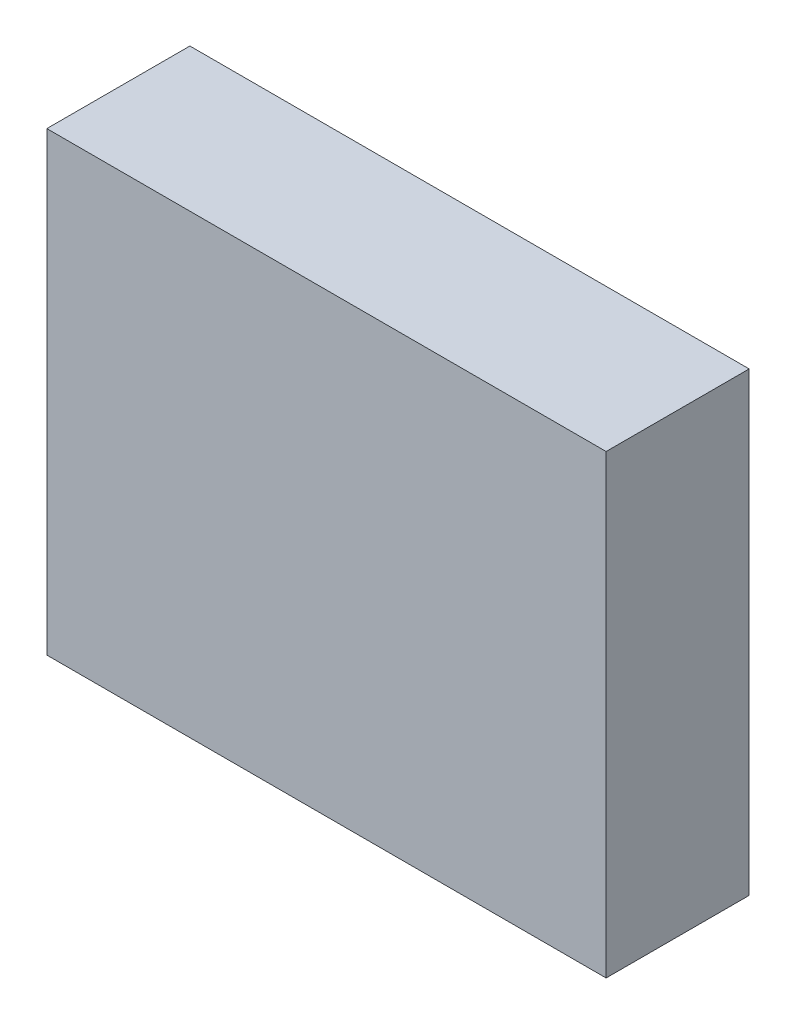
SolidWorks part; units mm, degrees
material "AISI 1020"
ref_plane "Plano superior" through (0, 0, 0) normal (0, 0, 1) x (1, 0, 0)
ref_plane "Plano frontal" through (0, 0, 0) normal (0, 1, 0) x (1, 0, 0)
ref_plane "Plano direito" through (0, 0, 0) normal (1, 0, 0) x (0, 0, -1)
other "Caixa delimitadora"
ref_plane "Default Plane" through (-78.1989, -63.755, 0) normal (0, 1, 0) x (1, 0, 0)
sketch "Esboço1" plane through (0, 0, 0) normal (0, 0, 1) x (1, 0, 0)
  line L1 (-78.1989, -63.755) -> (78.1989, -63.755)
  line L2 (-78.1989, -63.755) -> (-78.1989, 63.755)
  line L3 (-78.1989, 63.755) -> (78.1989, 63.755)
  line L4 (78.1989, -63.755) -> (78.1989, 63.755)
  line L5 (-78.1989, -63.755) -> (78.1989, 63.755) construction
  line L6 (-78.1989, 63.755) -> (78.1989, -63.755) construction
  circle A0 centre (0, 0) radius 15.125 construction
  point P0 (0, 0)
  dimension "D3" = 30.25
  dimension "D1" = 156.3979
  dimension "D2" = 127.51
extrude "Ressalto-extrusão1" add sketch "Esboço1" along normal blind 40
